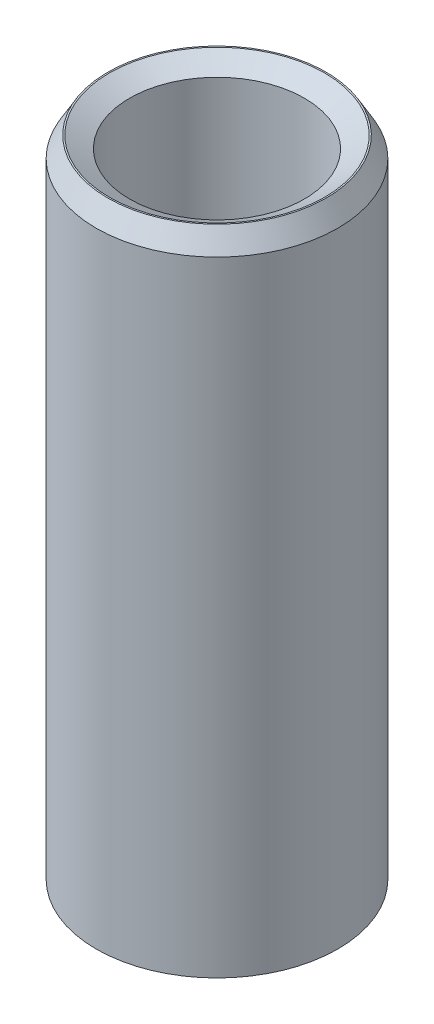
SolidWorks part; units mm, degrees
ref_plane "Front Plane" through (0, 0, 0) normal (0, 0, 1) x (1, 0, 0)
ref_plane "Top Plane" through (0, 0, 0) normal (0, 1, 0) x (1, 0, 0)
ref_plane "Right Plane" through (0, 0, 0) normal (1, 0, 0) x (0, 0, -1)
sketch "Sketch1" plane through (0, 0, 0) normal (0, 1, 0) x (1, 0, 0)
  circle A0 centre (0, 0) radius 12.5
  dimension "SLEEVE_OD" = 25
extrude "Boss-Extrude1" add sketch "Sketch1" along normal blind 67.8888
sketch "Sketch2" plane through (0, 0, 0) normal (0, 1, 0) x (1, 0, 0)
  circle A0 centre (0, 0) radius 9.0437
  dimension "BORE_D" = 18.0873
extrude "Cut-Extrude1" cut sketch "Sketch2" along normal through all
chamfer "Chamfer1" distance 2.0939 angle 30 4 edges at (0, 67.8888, 9.0437) (0, 0, 9.0437) (0, 0, 12.5) (0, 67.8888, 12.5) first distance on face at (0, 67.8888, 9.0437) first distance on face at (0, 0, 9.0437) first distance on face at (0, 67.8888, 12.5)
